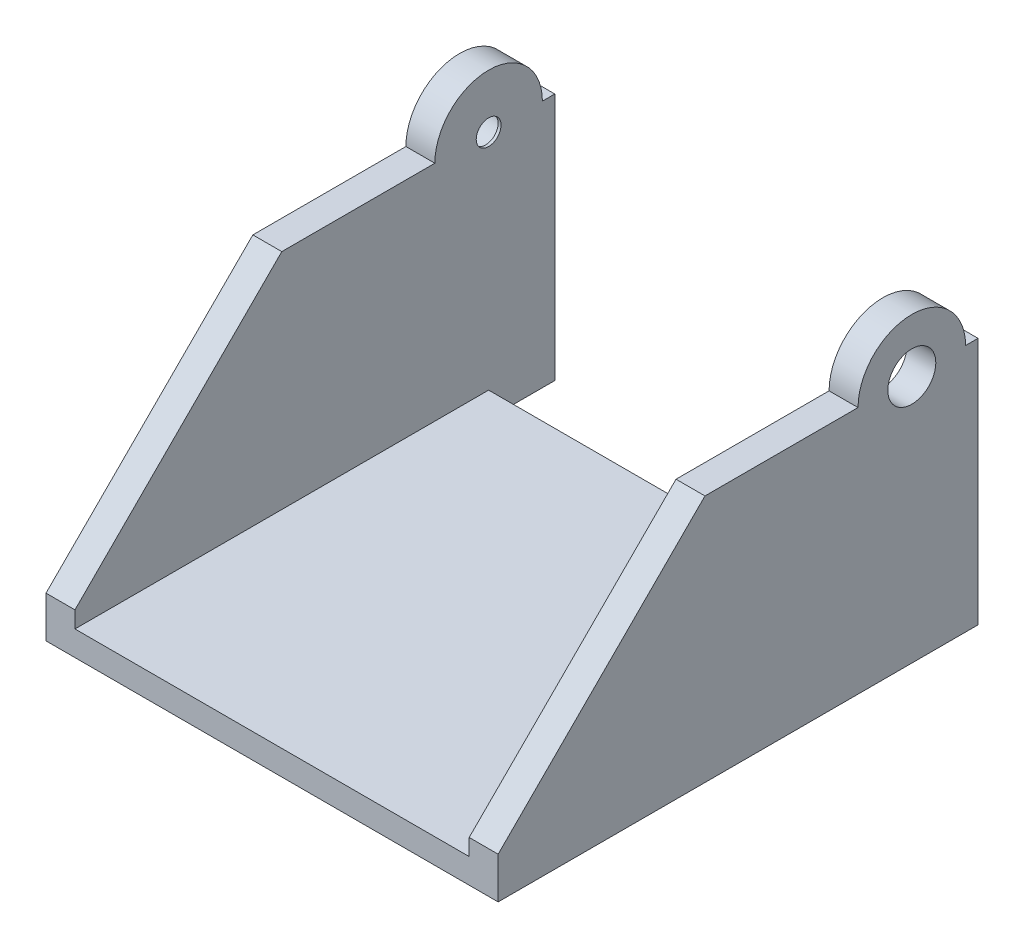
SolidWorks part; units mm, degrees
ref_plane "Front Plane" through (0, 0, 0) normal (0, 0, 1) x (1, 0, 0)
ref_plane "Top Plane" through (0, 0, 0) normal (0, 1, 0) x (1, 0, 0)
ref_plane "Right Plane" through (0, 0, 0) normal (1, 0, 0) x (0, 0, -1)
sketch "Sketch1" plane through (0, 0, 0) normal (0, 0, 1) x (1, 0, 0)
  line L0 (0, 0) -> (-23.825, 0) construction
  line L2 (-23.825, 0) -> (-27.325, 0)
  line L3 (-23.825, 0) -> (-23.825, -30)
  line L4 (-23.825, -30) -> (-27.325, -30)
  line L5 (-27.325, 0) -> (-27.325, -30)
  line L6 (-23.825, -30) -> (0, -30)
  line L7 (-23.825, -30) -> (-23.825, -27)
  line L8 (-23.825, -27) -> (0, -27)
  line L9 (0, -30) -> (0, -27)
  dimension "D1" = 23.825
  dimension "D2" = 3.5
  dimension "D3" = 30
  dimension "D4" = 3
extrude "Boss-Extrude1" add sketch "Sketch1" along normal blind 50 contours L2 L5 L4 L3 | L6 L9 L8 L3 region at (-25.575, -15, 0) region at (-11.9125, -28.5, 0)
sketch "Sketch2" plane through (-23.825, 0, 0) normal (1, 0, 0) x (0, 0, -1)
  line L1 (0, 0) -> (8, 0)
  line L2 (0, 0) -> (0, -30)
  line L3 (0, -30) -> (8, -30)
  line L4 (8, 0) -> (8, -30)
  circle A0 centre (0, 0) radius 1.5
  circle A1 centre (0, 0) radius 6.5
  line M1 (0, -27) -> (0, 0)
  line M2 (0, 0) -> (-50, 0)
  dimension "D1" = 3
  dimension "D2" = 13
  dimension "D3" = 8
extrude "Boss-Extrude2" add sketch "Sketch2" against normal blind 3.5 contours A1 L2 L3 L4 L1 M1 | L2 A1 L1 A0 | L1 A1 A0 M2 region at (-23.825, 2.8781, 0) region at (-23.825, -2.8781, -2.8781) region at (-23.825, -16.9641, -4.1992)
sketch "Sketch3" plane through (-27.325, 0, 0) normal (-1, 0, 0) x (0, 0, 1)
  circle A0 centre (0, 0) radius 1.5
extrude "Cut-Extrude1" cut sketch "Sketch3" against normal through all both and the other way through all
mirror "Mirror1" about plane through (0, 0, 50) normal (-1, 0, 0) of "Cut-Extrude1", "Boss-Extrude2", "Boss-Extrude1"
sketch "Sketch4" plane through (-27.325, 0, 0) normal (-1, 0, 0) x (0, 0, 1)
  circle A0 centre (0, 0) radius 2.5
  dimension "D1" = 5
extrude "Cut-Extrude2" cut sketch "Sketch4" against normal blind 3.15 and the other way through all
sketch "Sketch5" plane through (27.325, 0, 0) normal (1, 0, 0) x (0, 0, -1)
  circle A0 centre (0, 0) radius 2.9
  dimension "D1" = 5.8
extrude "Cut-Extrude3" cut sketch "Sketch5" against normal blind 7.15
sketch "Sketch6" plane through (-27.325, 0, 0) normal (-1, 0, 0) x (0, 0, 1)
  line L0 (50, -30) -> (-8, -30) construction
  line L1 (50, 0) -> (25, 0)
  line L2 (50, 0) -> (50, -25)
  line L3 (50, -25) -> (25, -25)
  line L4 (25, 0) -> (25, -25)
  line L5 (25, 0) -> (50, -25)
  line M4 (50, 0) -> (6.5, 0)
  line M9 (50, -30) -> (50, 0)
  dimension "D1" = 5
  dimension "D2" = 25
extrude "Cut-Extrude4" cut sketch "Sketch6" against normal blind 7.15 contours L5 M4 M9 region at (-27.325, -8.3333, 41.6667)
ref_plane "Plane1" through (0, 0, 0) normal (1, 0, 0) x (0, 0, -1)
mirror "Mirror2" about plane through (0, 0, 0) normal (1, 0, 0) of "Cut-Extrude4"
